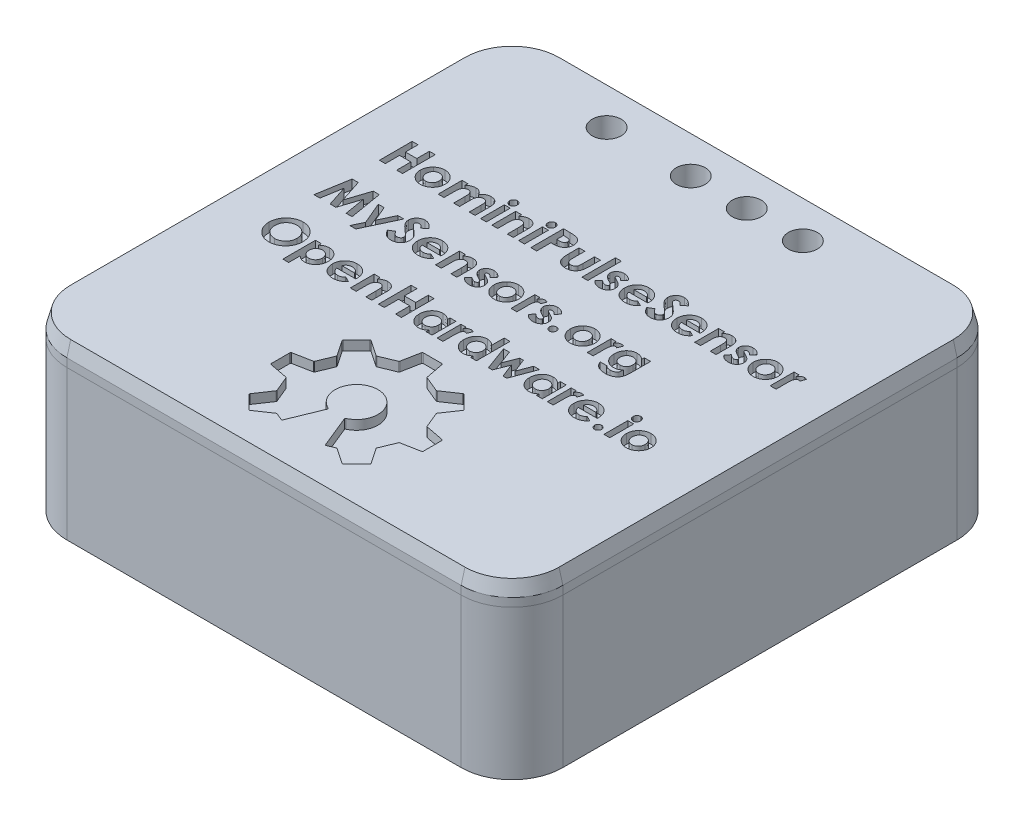
SolidWorks part; units mm, degrees
other "Base"
other "PCB"
other "Lid"
ref_plane "Front Plane" through (0, 0, 0) normal (0, 0, 1) x (1, 0, 0)
ref_plane "Top Plane" through (0, 0, 0) normal (0, 1, 0) x (1, 0, 0)
ref_plane "Right Plane" through (0, 0, 0) normal (1, 0, 0) x (0, 0, -1)
sketch "Sketch1" plane through (0, 0, 0) normal (0, 1, 0) x (1, 0, 0)
  line L1 (21.1, 25.1) -> (-21.1, 25.1)
  line L2 (25.1, 21.1) -> (25.1, -21.1)
  line L3 (21.1, -25.1) -> (-21.1, -25.1)
  line L4 (-25.1, 21.1) -> (-25.1, -21.1)
  line L5 (25.1, 25.1) -> (-25.1, -25.1) construction
  line L6 (25.1, -25.1) -> (-25.1, 25.1) construction
  line L10 (-26.54, 21.1) -> (-26.54, -21.1)
  line L11 (21.1, -26.54) -> (-21.1, -26.54)
  line L12 (26.54, 21.1) -> (26.54, -21.1)
  line L13 (21.1, 26.54) -> (-21.1, 26.54)
  circle A0 centre (-21, 21) radius 1.375
  circle A1 centre (-21, -21) radius 1.375
  circle A2 centre (21, 21) radius 1.375
  circle A3 centre (21, -21) radius 1.375
  arc A4 (-21.1, 25.1) -> (-25.1, 21.1) centre (-21.1, 21.1) ccw
  arc A5 (-21.1, -25.1) -> (-25.1, -21.1) centre (-21.1, -21.1) cw
  arc A6 (25.1, -21.1) -> (21.1, -25.1) centre (21.1, -21.1) cw
  arc A7 (21.1, 25.1) -> (25.1, 21.1) centre (21.1, 21.1) cw
  circle A8 centre (-21, 21) radius 2.375
  circle A9 centre (21, 21) radius 2.375
  circle A10 centre (21, -21) radius 1.775
  circle A11 centre (-21, -21) radius 2.375
  arc A12 (-21.1, -26.54) -> (-26.54, -21.1) centre (-21.1, -21.1) cw
  arc A13 (26.54, -21.1) -> (21.1, -26.54) centre (21.1, -21.1) cw
  arc A14 (21.1, 26.54) -> (26.54, 21.1) centre (21.1, 21.1) cw
  arc A15 (-21.1, 26.54) -> (-26.54, 21.1) centre (-21.1, 21.1) ccw
  point P0 (0, 0)
  dimension "D4" = 2.75
  dimension "D7" = 4.1
  dimension "D9" = 2.75
  dimension "D10" = 2.75
  dimension "D11" = 2.75
  dimension "D14" = 4
  dimension "D15" = 4
  dimension "D1" = 50.2
  dimension "D2" = 50.2
  dimension "D5" = 4.1
  dimension "D6" = 4.1
  dimension "D8" = 4.1
  dimension "D12" = 4.1
  dimension "D13" = 4.1
  dimension "D3" = 1
  dimension "D16" = 1.44
  dimension "D17" = 0.4
extrude "Boss-Extrude3" add sketch "Sketch1" along normal blind 13.99 contours L13 A15 L10 A12 L11 A13 L12 A14 L1 A7 L2 A6 L3 A5 L4 A4 region at (-24.4159, 0, -24.4159)
extrude "Boss-Extrude4" add sketch "Sketch1<3>" against normal blind 2 contours A7 L1 A4 L4 A5 L3 A6 L2 A11 A10 A9 A8 | L13 A15 L10 A12 L11 A13 L12 A14 L1 A7 L2 A6 L3 A5 L4 A4 | A11 A1 | A1 | A10 A3 | A3 | A8 A0 | A0 | A9 A2 | A2 region at (0.0672, 0, 0.0672) region at (-24.4159, 0, -24.4159) region at (-21, 0, -21) region at (-21, 0, 21) region at (21, 0, -21) region at (21, 0, 21) region at (-23.3078, 0, -21) region at (18.6922, 0, -21) region at (19.2752, 0, 21) region at (-23.3078, 0, 21)
sketch "Sketch1<3>" plane through (0, 0, 0) normal (0, 1, 0) x (1, 0, 0) same geometry as "Sketch1"
extrude "Boss-Extrude5" add sketch "Sketch1<4>" along normal blind 12.99 contours A3 | A1 | A2 | A0 region at (-21, 0, -21) region at (-21, 0, 21) region at (21, 0, -21) region at (21, 0, 21)
sketch "Sketch1<4>" plane through (0, 0, 0) normal (0, 1, 0) x (1, 0, 0) same geometry as "Sketch1"
extrude "Boss-Extrude6" add sketch "Sketch1<5>" along normal blind 7 contours A11 A1 | A8 A0 | A10 A3 | A9 A2 region at (-23.3078, 0, -21) region at (18.6922, 0, -21) region at (19.2752, 0, 21) region at (-23.3078, 0, 21)
sketch "Sketch1<5>" plane through (0, 0, 0) normal (0, 1, 0) x (1, 0, 0) same geometry as "Sketch1"
sketch "Sketch4" plane through (0, 7, 0) normal (0, 1, 0) x (1, 0, 0)
  line L1 (-21, 25) -> (21, 25)
  line L2 (-25, 21) -> (-25, -21)
  line L3 (-21, -25) -> (21, -25)
  line L4 (25, 21) -> (25, -21)
  line L5 (-25, 25) -> (25, -25) construction
  line L6 (-25, -25) -> (25, 25) construction
  arc A0 (-25, -21) -> (-21, -25) centre (-21, -21) ccw
  arc A1 (21, -25) -> (25, -21) centre (21, -21) ccw
  arc A2 (21, 25) -> (25, 21) centre (21, 21) cw
  arc A3 (-21, 25) -> (-25, 21) centre (-21, 21) ccw
  circle A4 centre (-21, 21) radius 1.4
  circle A5 centre (21, 21) radius 1.4
  circle A6 centre (21, -21) radius 1.4
  circle A7 centre (-21, -21) radius 1.4
  point P0 (0, 0)
  dimension "D3" = 4
  dimension "D4" = 2.8
  dimension "D5" = 2.8
  dimension "D6" = 2.8
  dimension "D7" = 2.8
  dimension "D1" = 50
  dimension "D2" = 50
  dimension "D8" = 4
  dimension "D9" = 4
  dimension "D10" = 4
  dimension "D11" = 4
extrude "Boss-Extrude7" add sketch "Sketch4" along normal blind 1.6 separate body
sketch "Sketch5" plane through (0, 8.6, 0) normal (0, 1, 0) x (1, 0, 0)
  line L0 (-21, -25) -> (21, -25) construction
  line L1 (-25, -9.2) -> (-19.2, -9.2)
  line L2 (-25, -9.2) -> (-25, -16.8)
  line L3 (-25, -16.8) -> (-19.2, -16.8)
  line L4 (-19.2, -9.2) -> (-19.2, -16.8)
  line L5 (-25, -9.2) -> (-19.2, -16.8) construction
  line L6 (-25, -16.8) -> (-19.2, -9.2) construction
  line L7 (-25, 3.8) -> (-19.2, 3.8)
  line L8 (-25, 3.8) -> (-25, -3.8)
  line L9 (-25, -3.8) -> (-19.2, -3.8)
  line L10 (-19.2, 3.8) -> (-19.2, -3.8)
  line L11 (-25, 3.8) -> (-19.2, -3.8) construction
  line L12 (-25, -3.8) -> (-19.2, 3.8) construction
  line L13 (-25, 21) -> (-25, -21) construction
  point P0 (-22.1, -13)
  point P5 (-22.1, 0)
  dimension "D4" = 7.6
  dimension "D5" = 5.8
  dimension "D6" = 5.8
  dimension "D7" = 7.6
  dimension "D8" = 12
  dimension "D9" = 25
extrude "Boss-Extrude8" add sketch "Sketch5" along normal blind 2.8
sketch "Sketch6" plane through (0, 8.6, 0) normal (0, 1, 0) x (1, 0, 0)
  line L0 (-25, 21) -> (-25, 3.8) construction
  line L1 (-21, -25) -> (21, -25) construction
  circle A0 centre (-12.0645, 22.1935) radius 1.55
  circle A1 centre (-3.0645, 22.1935) radius 1.55
  circle A2 centre (2.9355, 22.1935) radius 1.55
  circle A3 centre (8.9355, 22.1935) radius 1.55
  dimension "D1" = 3.1
  dimension "D2" = 12.9355
  dimension "D8" = 33.9355
  dimension "D3" = 47.1935
  dimension "D4" = 21.9355
  dimension "D5" = 47.1935
  dimension "D6" = 27.9355
  dimension "D7" = 47.1935
  dimension "D9" = 47.1935
extrude "Boss-Extrude9" add sketch "Sketch6" along normal blind 5
sketch "Sketch11" plane through (-26.54, 0, 0) normal (-1, 0, 0) x (0, 0, 1)
  line L4 (13, 11.4) -> (13, 8.6) construction
  line L6 (18.967, 6) -> (-6.033, 6)
  line L7 (18.967, 6) -> (18.967, 14)
  line L8 (18.967, 14) -> (-6.033, 14)
  line L9 (-6.033, 6) -> (-6.033, 14)
  line L11 (18.967, 6) -> (-6.033, 14) construction
  line L12 (0, 11.4) -> (0, 8.6) construction
  line L13 (-3.8, 10) -> (16.734, 10) construction
  line L14 (18.967, 14) -> (-6.033, 6) construction
  point P0 (0, 10)
  point P2 (6.467, 10)
  point P6 (13, 10)
  point P14 (6.467, 10)
  dimension "D1" = 25
  dimension "D3" = 8
extrude "Cut-Extrude1" cut sketch "Sketch11" against normal up to surface (1.44 mm away) up to face at (-25.1, 6.995, 0)
sketch "Sketch13" plane through (0, 13.99, 0) normal (0, 1, 0) x (1, 0, 0)
  line L0 (21.1, -26.54) -> (-21.1, -26.54) construction
  line L1 (26.54, 21.1) -> (26.54, -21.1) construction
  line L2 (21.1, 26.54) -> (-21.1, 26.54) construction
  line L4 (21.1, -26.54) -> (-21.1, -26.54)
  line L5 (26.54, 21.1) -> (26.54, -21.1)
  line L6 (21.1, 26.54) -> (-21.1, 26.54)
  line L7 (-26.54, -21.1) -> (-26.54, 21.1)
  arc A0 (-26.54, -21.1) -> (-21.1, -26.54) centre (-21.1, -21.1) ccw construction
  arc A1 (21.1, -26.54) -> (26.54, -21.1) centre (21.1, -21.1) ccw construction
  arc A2 (26.54, 21.1) -> (21.1, 26.54) centre (21.1, 21.1) ccw construction
  arc A3 (-21.1, 26.54) -> (-26.54, 21.1) centre (-21.1, 21.1) ccw construction
  arc A4 (-26.54, -21.1) -> (-21.1, -26.54) centre (-21.1, -21.1) ccw
  arc A5 (21.1, -26.54) -> (26.54, -21.1) centre (21.1, -21.1) ccw
  arc A6 (26.54, 21.1) -> (21.1, 26.54) centre (21.1, 21.1) ccw
  arc A7 (-21.1, 26.54) -> (-26.54, 21.1) centre (-21.1, 21.1) ccw
  circle A8 centre (8.9355, 22.1935) radius 1.55 construction
  circle A9 centre (2.9355, 22.1935) radius 1.55 construction
  circle A10 centre (-3.0645, 22.1935) radius 1.55 construction
  circle A11 centre (-12.0645, 22.1935) radius 1.55 construction
  circle A12 centre (8.9355, 22.1935) radius 1.55
  circle A13 centre (2.9355, 22.1935) radius 1.55
  circle A14 centre (-3.0645, 22.1935) radius 1.55
  circle A15 centre (-12.0645, 22.1935) radius 1.55
extrude "Boss-Extrude11" add sketch "Sketch13" along normal blind 2.4 separate body
chamfer "Chamfer1" distance 1.5 distance2 0.4 8 edges at (24.9467, 16.39, 24.9467) (26.54, 16.39, 0) (0, 16.39, 26.54) (24.9467, 16.39, -24.9467) (-24.9467, 16.39, 24.9467) (0, 16.39, -26.54) (-26.54, 16.39, 0) (-24.9467, 16.39, -24.9467) first distance on face at (24.3833, 15.19, 24.3833) first distance on face at (26.54, 15.19, 0) first distance on face at (0, 15.19, 26.54) first distance on face at (24.3833, 15.19, -24.3833) first distance on face at (-24.3833, 15.19, 24.3833) first distance on face at (0, 15.19, -26.54) first distance on face at (-26.54, 15.19, 0) first distance on face at (-24.3833, 15.19, -24.3833)
sketch "Sketch16" plane through (0, 13.99, 0) normal (0, -1, 0) x (1, 0, 0)
  circle A0 centre (21, 21) radius 1.4 construction
  circle A1 centre (21, 21) radius 1.4
  circle A2 centre (-21, 21) radius 1.4 construction
  circle A3 centre (-21, 21) radius 1.4
  circle A4 centre (21, -21) radius 1.4 construction
  circle A5 centre (21, -21) radius 1.4
  circle A6 centre (-21, -21) radius 1.4 construction
  circle A7 centre (-21, -21) radius 1.4
  circle A8 centre (-21, -21) radius 2.375 construction
  circle A9 centre (21, -21) radius 2.375 construction
  circle A11 centre (-21, 21) radius 2.375 construction
  circle A12 centre (-21, -21) radius 2.375
  circle A13 centre (21, -21) radius 2.375
  circle A14 centre (21, 21) radius 2.38
  circle A15 centre (-21, 21) radius 2.375
  dimension "D1" = 0.98
extrude "Boss-Extrude14" add sketch "Sketch16" along normal blind 2
sketch "Sketch17" plane through (0, 13.99, 0) normal (0, -1, 0) x (1, 0, 0)
  line L0 (-21.1, 23.1) -> (21.1, 23.1)
  line L1 (23.1, -21.1) -> (23.1, 21.1)
  line L2 (-21.1, 25.1) -> (21.1, 25.1)
  line L3 (-21.1, 25.1) -> (21.1, 25.1)
  line L4 (-21.1, -23.1) -> (-14.8497, -23.1)
  line L5 (-23.1, 21.1) -> (-23.1, 18.967)
  line L6 (-23.1, 18.967) -> (-24.1, 18.967)
  line L7 (-23.1, -21.1) -> (-25.1, -21.1)
  line L8 (12.271, -23.1) -> (12.271, -25.1)
  line L9 (-14.8497, -23.1) -> (-14.8497, -25.1)
  line L10 (12.271, -23.1) -> (21.1, -23.1)
  line L11 (12.271, -25.1) -> (21.1, -25.1)
  line L12 (-21.1, -23.1) -> (21.1, -23.1) construction
  line L14 (-21.1, -25.1) -> (21.1, -25.1) construction
  line L18 (-25.1, 21.1) -> (-25.1, -21.1)
  line L19 (-21.1, -25.1) -> (21.1, -25.1)
  line L20 (25.1, -21.1) -> (25.1, 21.1)
  line L21 (-25.1, 21.1) -> (-25.1, 18.967)
  line L22 (-21.1, -25.1) -> (-14.8497, -25.1)
  line L23 (25.1, -21.1) -> (25.1, 21.1)
  line L26 (-25.1, 18.967) -> (-24.1, 18.967)
  arc A0 (-21.1, 23.1) -> (-23.1, 21.1) centre (-21.1, 21.1) ccw
  arc A1 (23.1, 21.1) -> (21.1, 23.1) centre (21.1, 21.1) ccw
  arc A2 (21.1, -23.1) -> (23.1, -21.1) centre (21.1, -21.1) ccw
  arc A3 (-23.1, -21.1) -> (-21.1, -23.1) centre (-21.1, -21.1) ccw
  arc A20 (-21.1, 25.1) -> (-25.1, 21.1) centre (-21.1, 21.1) ccw
  arc A21 (-25.1, -21.1) -> (-21.1, -25.1) centre (-21.1, -21.1) ccw
  arc A22 (21.1, -25.1) -> (25.1, -21.1) centre (21.1, -21.1) ccw
  arc A23 (25.1, 21.1) -> (21.1, 25.1) centre (21.1, 21.1) ccw
  arc A24 (-21.1, 25.1) -> (-25.1, 21.1) centre (-21.1, 21.1) ccw
  arc A25 (-25.1, -21.1) -> (-21.1, -25.1) centre (-21.1, -21.1) ccw
  arc A26 (21.1, -25.1) -> (25.1, -21.1) centre (21.1, -21.1) ccw
  arc A27 (25.1, 21.1) -> (21.1, 25.1) centre (21.1, 21.1) ccw
  point P11 (-24.1, -21.1)
  point P12 (-24.1, 21.1)
  dimension "D1" = 1.44
  dimension "D2" = 1.44
  dimension "D4" = 2
extrude "Boss-Extrude15" add sketch "Sketch17" along normal blind 2
chamfer "Chamfer2" distance 1 distance2 0.2 7 edges at (23.9284, 11.99, -23.9284) (25.1, 11.99, 0) (23.9284, 11.99, 23.9284) (0, 11.99, 25.1) (-23.9284, 11.99, 23.9284) (-25.1, 11.99, 20.0335) (16.6855, 11.99, -25.1) first distance on face at (23.5142, 12.99, -23.5142) first distance on face at (25.1, 12.99, 0) first distance on face at (23.5142, 12.99, 23.5142) first distance on face at (0, 12.99, 25.1) first distance on face at (-23.5142, 12.99, 23.5142) first distance on face at (-25.1, 12.99, 20.0335) first distance on face at (16.6855, 12.99, -25.1)
chamfer "Chamfer3" distance 0.2 distance2 0.5 3 edges at (21, 11.99, -22.4) (-21, 11.99, -22.4) (-21, 11.99, 19.6) first distance on face at (4.0085, 11.99, 4.8455) first distance on face at (-19.6961, 11.99, -22.7115)
sketch "Sketch18" plane through (0, 16.39, 0) normal (0, 1, 0) x (1, 0, 0)
  text T0 "<b>HominiPulseSensor</b>\r\n<b>MySensors.org</b>\r\n<b>OpenHardware.io</b>"
extrude "Cut-Extrude2" cut sketch "Sketch18" against normal blind 1
sketch "Sketch19" plane through (0, 16.39, 0) normal (0, 1, 0) x (1, 0, 0)
  line L118 (-0.9074, -18.8582) -> (-2.2849, -22.232)
  line L119 (-2.4223, -22.2893) -> (-3.1705, -21.9794)
  line L120 (-3.2696, -21.9894) -> (-4.9151, -23.1027)
  line L121 (-5.0482, -23.09) -> (-6.4541, -21.684)
  line L122 (-6.4668, -21.5509) -> (-5.3535, -19.9054)
  line L123 (-5.3435, -19.8064) -> (-6.0203, -18.1724)
  line L124 (-6.0974, -18.1095) -> (-8.0482, -17.7331)
  line L125 (-8.1333, -17.63) -> (-8.1333, -15.6417)
  line L126 (-8.0482, -15.5386) -> (-6.0974, -15.1623)
  line L127 (-6.0203, -15.0993) -> (-5.3435, -13.4653)
  line L128 (-5.3535, -13.3663) -> (-6.4668, -11.7208)
  line L129 (-6.4541, -11.5877) -> (-5.0482, -10.1818)
  line L130 (-4.9151, -10.169) -> (-3.2696, -11.2823)
  line L131 (-3.1705, -11.2924) -> (-1.5365, -10.6155)
  line L132 (-1.4736, -10.5384) -> (-1.0972, -8.5876)
  line L133 (-0.9941, -8.5025) -> (0.9941, -8.5025)
  line L134 (1.0972, -8.5876) -> (1.4736, -10.5384)
  line L135 (1.5365, -10.6155) -> (3.1705, -11.2924)
  line L136 (3.2696, -11.2823) -> (4.9151, -10.169)
  line L137 (5.0482, -10.1818) -> (6.4541, -11.5877)
  line L138 (6.4668, -11.7208) -> (5.3535, -13.3663)
  line L139 (5.3435, -13.4653) -> (6.0203, -15.0993)
  line L140 (6.0974, -15.1623) -> (8.0482, -15.5386)
  line L141 (8.1333, -15.6417) -> (8.1333, -17.63)
  line L142 (8.0482, -17.7331) -> (6.0974, -18.1095)
  line L143 (6.0203, -18.1724) -> (5.3435, -19.8064)
  line L144 (5.3535, -19.9054) -> (6.4668, -21.5509)
  line L145 (6.4541, -21.684) -> (5.0482, -23.09)
  line L146 (4.9151, -23.1027) -> (3.2696, -21.9894)
  line L147 (3.1705, -21.9794) -> (2.4223, -22.2893)
  line L148 (2.2849, -22.232) -> (0.9074, -18.8582)
  arc A468 (0.9607, -18.7231) -> (-0.9607, -18.7231) centre (0, -16.6359) ccw
  arc A469 (-0.9074, -18.8582) -> (-0.9607, -18.7231) centre (-1.0046, -18.8185) ccw
  arc A470 (-2.4223, -22.2893) -> (-2.2849, -22.232) centre (-2.3821, -22.1923) ccw
  arc A471 (-3.1705, -21.9794) -> (-3.2696, -21.9894) centre (-3.2107, -22.0764) ccw
  arc A472 (-5.0482, -23.09) -> (-4.9151, -23.1027) centre (-4.9739, -23.0157) ccw
  arc A473 (-6.4668, -21.5509) -> (-6.4541, -21.684) centre (-6.3799, -21.6098) ccw
  arc A474 (-5.3535, -19.9054) -> (-5.3435, -19.8064) centre (-5.4405, -19.8466) ccw
  arc A475 (-6.0203, -18.1724) -> (-6.0974, -18.1095) centre (-6.1173, -18.2126) ccw
  arc A476 (-8.1333, -17.63) -> (-8.0482, -17.7331) centre (-8.0283, -17.63) ccw
  arc A477 (-8.0482, -15.5386) -> (-8.1333, -15.6417) centre (-8.0283, -15.6417) ccw
  arc A478 (-6.0974, -15.1623) -> (-6.0203, -15.0993) centre (-6.1173, -15.0592) ccw
  arc A479 (-5.3435, -13.4653) -> (-5.3535, -13.3663) centre (-5.4405, -13.4251) ccw
  arc A480 (-6.4541, -11.5877) -> (-6.4668, -11.7208) centre (-6.3799, -11.6619) ccw
  arc A481 (-4.9151, -10.169) -> (-5.0482, -10.1818) centre (-4.9739, -10.256) ccw
  arc A482 (-3.2696, -11.2823) -> (-3.1705, -11.2924) centre (-3.2107, -11.1954) ccw
  arc A483 (-1.5365, -10.6155) -> (-1.4736, -10.5384) centre (-1.5767, -10.5185) ccw
  arc A484 (-0.9941, -8.5025) -> (-1.0972, -8.5876) centre (-0.9941, -8.6075) ccw
  arc A485 (1.0972, -8.5876) -> (0.9941, -8.5025) centre (0.9941, -8.6075) ccw
  arc A486 (1.4736, -10.5384) -> (1.5365, -10.6155) centre (1.5767, -10.5185) ccw
  arc A487 (3.1705, -11.2924) -> (3.2696, -11.2823) centre (3.2107, -11.1954) ccw
  arc A488 (5.0482, -10.1818) -> (4.9151, -10.169) centre (4.9739, -10.256) ccw
  arc A489 (6.4668, -11.7208) -> (6.4541, -11.5877) centre (6.3799, -11.6619) ccw
  arc A490 (5.3535, -13.3663) -> (5.3435, -13.4653) centre (5.4405, -13.4251) ccw
  arc A491 (6.0203, -15.0993) -> (6.0974, -15.1623) centre (6.1173, -15.0592) ccw
  arc A492 (8.1333, -15.6417) -> (8.0482, -15.5386) centre (8.0283, -15.6417) ccw
  arc A493 (8.0482, -17.7331) -> (8.1333, -17.63) centre (8.0283, -17.63) ccw
  arc A494 (6.0974, -18.1095) -> (6.0203, -18.1724) centre (6.1173, -18.2126) ccw
  arc A495 (5.3435, -19.8064) -> (5.3535, -19.9054) centre (5.4405, -19.8466) ccw
  arc A496 (6.4541, -21.684) -> (6.4668, -21.5509) centre (6.3799, -21.6098) ccw
  arc A497 (4.9151, -23.1027) -> (5.0482, -23.09) centre (4.9739, -23.0157) ccw
  arc A498 (3.2696, -21.9894) -> (3.1705, -21.9794) centre (3.2107, -22.0764) ccw
  arc A499 (2.2849, -22.232) -> (2.4223, -22.2893) centre (2.3821, -22.1923) ccw
  arc A500 (0.9607, -18.7231) -> (0.9074, -18.8582) centre (1.0046, -18.8185) ccw
extrude "Cut-Extrude3" cut sketch "Sketch19" against normal blind 1
